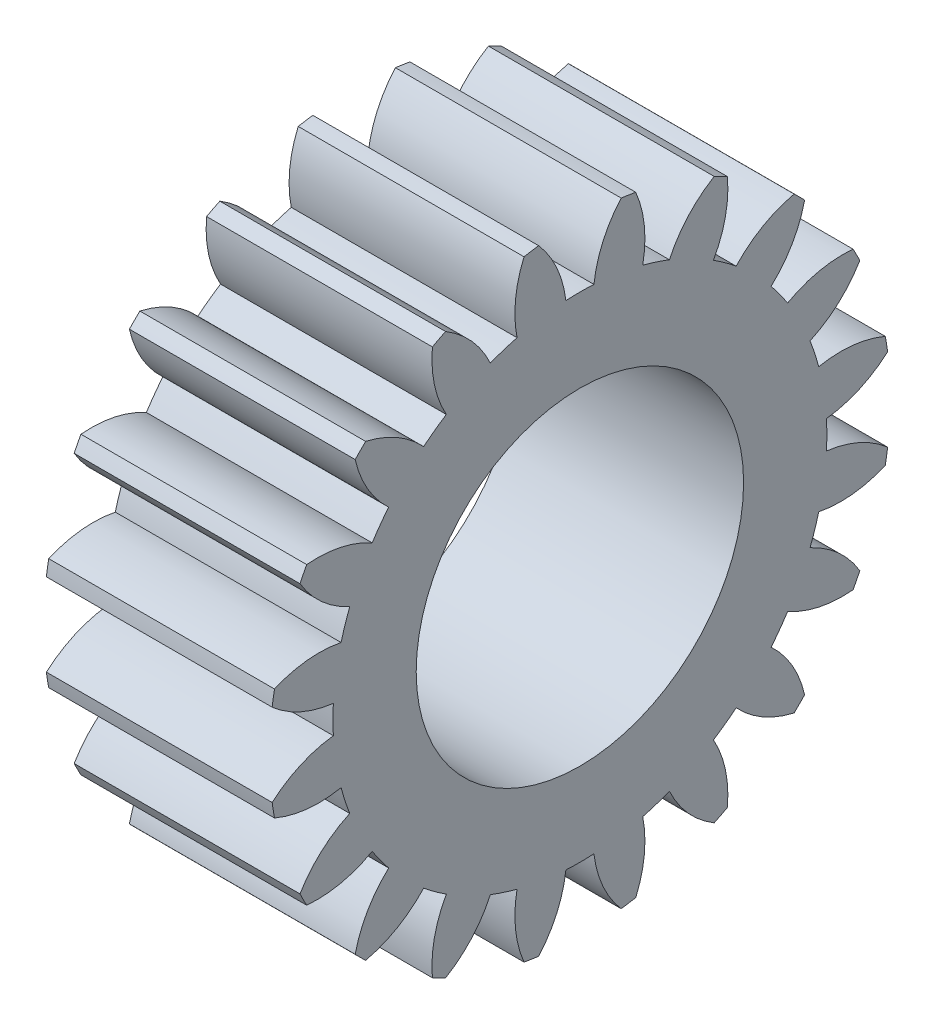
SolidWorks part; units mm, degrees
ref_plane "Plane1" through (0, 0, 0) normal (0, 0, 1) x (1, 0, 0)
ref_plane "Plane2" through (0, 0, 0) normal (0, 1, 0) x (1, 0, 0)
ref_plane "Plane3" through (0, 0, 0) normal (1, 0, 0) x (0, 0, -1)
sketch "HoldingSke" plane through (0, 0, 0) normal (0, 1, 0) x (1, 0, 0)
  line L0 (0, 0) -> (0.7518, -0.2736)
  line L1 (-15, 0) -> (100, 0) construction
  line L2 (0, 0) -> (-2.1039, 2.3779)
  line L3 (0, 0) -> (-11.863, 4.5341)
  line L4 (0, 0) -> (8.1152, 2.9537)
  line L5 (0, 0) -> (-46.8476, -17.4728)
  line L6 (0, 0) -> (-8.2896, -5.593)
  line L7 (-2.1039, 2.3779) -> (8.6586, 51.2059)
  line L8 (-76.2, 54.61) -> (-73.9, 54.61)
  line L9 (-71.009, 38.7566) -> (-53.1078, 45.2721)
  line L10 (-76.2, 71.12) -> (104.1128, 71.12)
  line L11 (0, 0) -> (-10, 0)
  line L12 (-76.2, 101.6) -> (-76.155, 101.6)
  line L13 (24.9733, 27.94) -> (52.9518, 28.4284)
  line L14 (24.9733, 27.94) -> (24.9743, 27.94)
  line L15 (24.9733, 27.94) -> (100.4006, 29.5858)
  line L16 (-63.627, -1.25) -> (-12.827, -1.25)
  circle A0 centre (0, 0) radius 7
  circle A1 centre (0, 0) radius 10.9365
  circle A2 centre (0, 0) radius 37.5
  circle A3 centre (0, 0) radius 7
  dimension "MHD" = 21.873
  dimension "Hub_dia" = 75
  dimension "Bore" = 14
  dimension "MBD" = 14
  dimension "Num_teeth" = 20
  dimension "Pitch" = 0.8
  dimension "Overall_len" = 50
  dimension "Show_teeth" = 20
  dimension "Thickness" = 10
  dimension "OAL" = 50.0001
  dimension "T_dim" = 2.3
  dimension "Ap" = 20
  dimension "H" = 19.05
  dimension "Pitch_radius" = 180.3128
  dimension "Width" = 10
  dimension "Backlash" = 0.045
  dimension "Addendum_fac" = 1
  dimension "Dedendum_fac" = 1.25
  dimension "Clearance_fac" = 0.25
  dimension "Dedendum_add" = 0.001
  dimension "Module" = 1.25
sketch "BasProSke" plane through (0, 0, 0) normal (0, 1, 0) x (1, 0, 0)
  line L0 (-10, 0) -> (60, 0) construction
  line L1 (0, 0) -> (0, 13.75)
  line L2 (0, 0) -> (10, 0)
  line L3 (10, 0) -> (10, 13.75)
  line L4 (10, 13.75) -> (0, 13.75)
  dimension "Thickness" = 10
  dimension "Diameter" = 27.5
revolve "Base-Revolve" add sketch "BasProSke" angle 360 about L0
sketch "TooCutSke" plane through (0, 0, 0) normal (1, 0, 0) x (0, 0, -1)
  line L1 (0, 0) -> (0, 107) construction
  line L2 (0, 0) -> (-1.0594, 12.455) construction
  line L3 (0, 0) -> (-3.9007, 24.6278) construction
  line L4 (-1.0594, 12.455) -> (-1.9503, 12.3139) construction
  arc A0 (0.6211, 10.9188) -> (-0.6211, 10.9188) centre (0, 0) ccw
  arc A1 (1.8466, 13.6511) -> (-1.8466, 13.6511) centre (0, 0) ccw
  circle A2 centre (0, 0) radius 12.5 construction
  circle A3 centre (0, 0) radius 11.7462 construction
  arc A4 (-0.6211, 10.9188) -> (-1.8466, 13.6511) centre (-5.5866, 10.3326) ccw
  arc A5 (1.8466, 13.6511) -> (0.6211, 10.9188) centre (5.5866, 10.3326) ccw
  dimension "Root_dia" = 21.873
  dimension "Overcut_dia" = 27.5508
  dimension "Pitch_dia" = 25
  dimension "Base_dia" = 23.4923
  dimension "Flank_rad" = 5
  dimension "Half_ang" = 9
  dimension "Half_CT" = 0.902
extrude "ToothCut" cut sketch "TooCutSke" along normal through all
fillet "Breaks" [suppressed] radius 0.025 tangent propagation no
fillet "RootFillets" [suppressed] radius 0.3135
pattern_circular "TeethCuts" count 20 every 18 about axis through (-10, 0, 0) along (1, 0, 0) of "ToothCut", "RootFillets", "Breaks"
sketch "HubNeaOneSke" plane through (0, 0, 0) normal (-1, 0, 0) x (0, 0, 1)
  circle A0 centre (0, 0) radius 10.9365
  dimension "Diameter" = 21.873
extrude "HubNearOne" [suppressed] add sketch "HubNeaOneSke" along normal blind 40.0001
sketch "HubNeaBotSke" plane through (0, 0, 0) normal (-1, 0, 0) x (0, 0, 1)
  circle A0 centre (0, 0) radius 10.9365
  dimension "Diameter" = 21.873
extrude "HubNearBoth" [suppressed] add sketch "HubNeaBotSke" along normal blind 20
ref_plane "FarPln" through (10, 0, 0) normal (1, 0, 0) x (0, 0, -1)
sketch "HubFarSke" plane through (10, 0, 0) normal (1, 0, 0) x (0, 0, -1)
  circle A0 centre (0, 0) radius 10.9365
  dimension "Diameter" = 21.873
extrude "HubFar" [suppressed] add sketch "HubFarSke" along normal blind 20
sketch "BorSke" plane through (0, 0, 0) normal (1, 0, 0) x (0, 0, -1)
  circle A0 centre (0, 0) radius 7
  dimension "Diameter" = 14
extrude "Bore" cut sketch "BorSke" along normal mid plane 100.0001
sketch "KeySke" plane through (0, 0, 0) normal (1, 0, 0) x (0, 0, -1)
  line L0 (-2.5, 0) -> (-2.5, 9.3)
  line L1 (-2.5, 9.3) -> (2.5, 9.3)
  line L2 (2.5, 9.3) -> (2.5, 0)
  line L3 (0, 0) -> (0, 34) construction
  line L4 (-2.5, 0) -> (2.5, 0)
  dimension "Offset" = 9.3
  dimension "Width" = 5
extrude "Keyway" [suppressed] cut sketch "KeySke" along normal mid plane 100.0001
pattern_circular "Keyway2" [suppressed] count 2 every 90 about axis through (-10, 0, 0) along (1, 0, 0) reverse direction yes
sketch "Sketch1" plane through (10, 0, 0) normal (1, 0, 0) x (0, 0, -1)
sketch "Sketch2" plane through (10, 0, 0) normal (1, 0, 0) x (0, 0, -1)
  circle A0 centre (0, 0) radius 7.25
  dimension "D1" = 14.5
extrude "Cut-Extrude1" cut sketch "Sketch2" against normal blind 10
equation "' \"Module@HoldingSke\" = 6.35"
equation "' \"Num_teeth@HoldingSke\" = 12"
equation "' \"Ap@HoldingSke\" =  20"
equation "' \"Ap@HoldingSke\" = 20"
equation "' \"Width@HoldingSke\" = 0.5 * 25.4"
equation "' \"Hub_dia@HoldingSke\"= 1 * 25.4"
equation "' \"Hub_dia@HoldingSke\" = 1 * 25.4"
equation "' \"Overall_len@HoldingSke\" = 1.0 * 25.4"
equation "' \"Bore@HoldingSke\" = 0.75 * 25.4"
equation "' \"T_dim@HoldingSke\" = 0.1 * 25.4"
equation "' \"Width@KeySke\" = 0.25 * 25.4"
equation "' \"Show_teeth@HoldingSke\" = 13"
equation "' \"Backlash@HoldingSke\" = 0.009 * 25.4"
equation "' \"Addendum_fac@HoldingSke\" = 1.0"
equation "' \"Dedendum_fac@HoldingSke\" = 1.25"
equation "' \"Dedendum_add@HoldingSke\" = 0.00005 * 25.4"
equation "' \"Clearance_fac@HoldingSke\" = 0.25"
equation "\"Pitch@HoldingSke\" = 1 / \"Module@HoldingSke\""
equation "\"Overcut_dia@TooCutSke\" = (\"Num_teeth@HoldingSke\" + 2 * \"Addendum_fac@HoldingSke\") / \"Pitch@HoldingSke\" + 0.002 * 25.4"
equation "\"Pitch_dia@TooCutSke\" = \"Num_teeth@HoldingSke\" / \"Pitch@HoldingSke\""
equation "\"Base_dia@TooCutSke\" = \"Num_teeth@HoldingSke\" / \"Pitch@HoldingSke\" * cos((\"Ap@HoldingSke\"  * 3.14159265 / 180))"
equation "\"Root_dia@TooCutSke\" = (\"Num_teeth@HoldingSke\" + 2) / \"Pitch@HoldingSke\" - 2 * (\"Addendum_fac@HoldingSke\" + \"Dedendum_fac@HoldingSke\") / \"Pitch@HoldingSke\" - \"Dedendum_add@HoldingSke\" * 2"
equation "\"Half_ang@TooCutSke\" = 180 / \"Num_teeth@HoldingSke\""
equation "\"Half_CT@TooCutSke\" = \"Num_teeth@HoldingSke\" / \"Pitch@HoldingSke\" * sin((3.14159265 / 2 / \"Num_teeth@HoldingSke\")) / 2 - 7 * \"Backlash@HoldingSke\" / 4"
equation "\"Flank_rad@TooCutSke\" = \"Num_teeth@HoldingSke\" / \"Pitch@HoldingSke\" / 5"
equation "\"Radius@RootFillets\" = \"Clearance_fac@HoldingSke\" / \"Pitch@HoldingSke\" + \"Dedendum_add@HoldingSke\""
equation "\"Break_rad@Breaks\" = 0.02 / \"Pitch@HoldingSke\""
equation "\"Thickness@HoldingSke\" = \"Width@HoldingSke\""
equation "\"OAL@HoldingSke\" = \"Thickness@HoldingSke\""
equation "\"MHD@HoldingSke\" = (\"Num_teeth@HoldingSke\" + 2) / \"Pitch@HoldingSke\" - 2 * (\"Addendum_fac@HoldingSke\" + \"Dedendum_fac@HoldingSke\")  / \"Pitch@HoldingSke\" - \"Dedendum_add@HoldingSke\" * 2"
equation "\"MBD@HoldingSke\" = (\"Num_teeth@HoldingSke\" + 2) / \"Pitch@HoldingSke\" - 2 * (\"Addendum_fac@HoldingSke\" + \"Dedendum_fac@HoldingSke\")  / \"Pitch@HoldingSke\" - \"Dedendum_add@HoldingSke\" * 2 - 0.002 * 25.4"
equation "\"MHD@HoldingSke\" = ((sgn( \"MHD@HoldingSke\" - \"Hub_dia@HoldingSke\" )-1)*( \"MHD@HoldingSke\" - \"Hub_dia@HoldingSke\" ))/-2+ \"Hub_dia@HoldingSke\""
equation "\"MBD@HoldingSke\" = ((sgn( \"MBD@HoldingSke\" - \"Bore@HoldingSke\" )-1)*( \"MBD@HoldingSke\" - \"Bore@HoldingSke\" ))/-2+ \"Bore@HoldingSke\""
equation "\"OAL@HoldingSke\" = ((sgn( \"OAL@HoldingSke\" - \"Overall_len@HoldingSke\" )+1)*( \"OAL@HoldingSke\" - \"Overall_len@HoldingSke\" ))/2 + \"Overall_len@HoldingSke\" + 0.000002 * 25.4"
equation "\"Num_teeth@TeethCuts\" = int( \"Show_teeth@HoldingSke\" ) + 1"
equation "\"Num_teeth@TeethCuts\" = ((sgn( \"Num_teeth@TeethCuts\" - \"Num_teeth@HoldingSke\" )-1)*( \"Num_teeth@TeethCuts\" - \"Num_teeth@HoldingSke\" ))/-2+ \"Num_teeth@HoldingSke\""
equation "\"Num_teeth@TeethCuts\" = ((sgn( \"Num_teeth@TeethCuts\" - 2.0)+1)*( \"Num_teeth@TeethCuts\" - 2.0))/2 +2.0"
equation "\"Angle@TeethCuts\" = 360.0 / \"Num_teeth@HoldingSke\""
equation "\"Diameter@BasProSke\" = (\"Num_teeth@HoldingSke\" + 2 * \"Addendum_fac@HoldingSke\") / \"Pitch@HoldingSke\""
equation "\"Thickness@BasProSke\"  = \"Thickness@HoldingSke\""
equation "' \"Fillet_rad@BasProSke\" =  \"Thickness@HoldingSke\" * 0.05"
equation "' \"Fillet_rad@BasProSke\" = \"Thickness@HoldingSke\" * 0.05"
equation "\"MHD@HoldingSke\" = ((sgn( \"MHD@HoldingSke\" - \"Root_dia@TooCutSke\" )-1)*( \"MHD@HoldingSke\" - \"Root_dia@TooCutSke\" ))/-2+ \"Root_dia@TooCutSke\""
equation "\"Diameter@HubNeaOneSke\" = \"MHD@HoldingSke\""
equation "\"Length@HubNearOne\" = \"OAL@HoldingSke\" - \"Thickness@BasProSke\""
equation "\"Diameter@HubNeaBotSke\" = \"MHD@HoldingSke\""
equation "\"Length@HubNearBoth\" = ( \"OAL@HoldingSke\" - \"Thickness@BasProSke\" ) / 2.0"
equation "\"Thickness@FarPln\" = \"Thickness@BasProSke\""
equation "\"Diameter@HubFarSke\" = \"MHD@HoldingSke\""
equation "\"Length@HubFar\" = ( \"OAL@HoldingSke\" - \"Thickness@BasProSke\" ) / 2.0"
equation "\"Diameter@BorSke\" = \"MBD@HoldingSke\""
equation "\"D1@Bore\" = \"OAL@HoldingSke\" * 2.0"
equation "\"D1@Keyway\" = \"OAL@HoldingSke\" * 2.0"
equation "\"Offset@KeySke\" = \"T_dim@HoldingSke\" + \"MBD@HoldingSke\" / 2.0"
